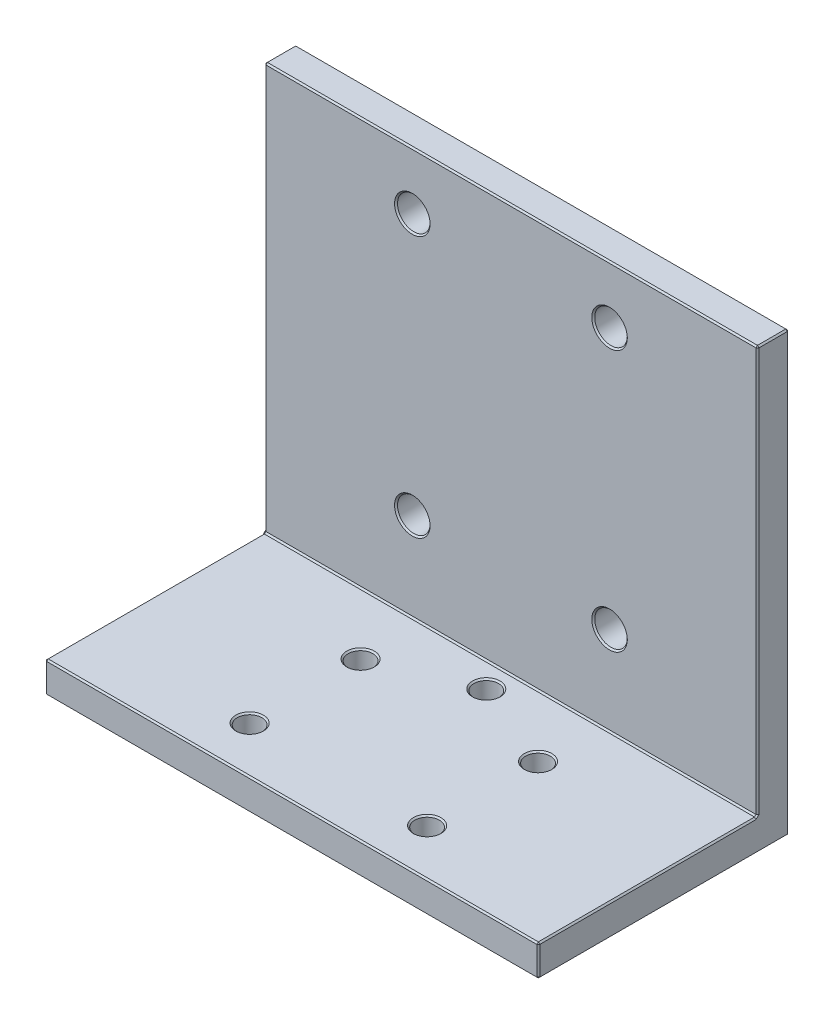
SolidWorks part; units mm, degrees
material "1060 Alloy"
ref_plane "Front Plane" through (0, 0, 0) normal (0, 0, 1) x (1, 0, 0)
ref_plane "Top Plane" through (0, 0, 0) normal (0, 1, 0) x (1, 0, 0)
ref_plane "Right Plane" through (0, 0, 0) normal (1, 0, 0) x (0, 0, -1)
sketch "Sketch1" plane through (0, 0, 0) normal (1, 0, 0) x (0, 0, -1)
  line L2 (0, 0) -> (0, 88.9)
  line L3 (0, 88.9) -> (-6.35, 88.9)
  line L4 (-6.35, 6.35) -> (-6.35, 88.9)
  line L5 (0, 0) -> (-50.8, 0)
  line L7 (-6.35, 6.35) -> (-50.8, 6.35)
  line L8 (-50.8, 0) -> (-50.8, 6.35)
  dimension "D1" = 6.35
  dimension "D2" = 88.9
  dimension "D3" = 50.8
extrude "Boss-Extrude1" add sketch "Sketch1" along normal mid plane 100
sketch "Sketch2" plane through (0, 0, 6.35) normal (0, 0, 1) x (1, 0, 0)
  line L0 (50, 0) -> (-50, 0) construction
  line L1 (20, 24.3) -> (-20, 24.3) construction
  line L2 (20, 24.3) -> (20, 77.3) construction
  line L3 (20, 77.3) -> (-20, 77.3) construction
  line L4 (-20, 24.3) -> (-20, 77.3) construction
  line L5 (20, 24.3) -> (-20, 77.3) construction
  line L6 (20, 77.3) -> (-20, 24.3) construction
  line L7 (50, 88.9) -> (50, 6.35) construction
  line L8 (0, 50.8) -> (0, 0) construction
  line L9 (-50, 101.6) -> (50, 101.6) construction
  line L10 (-50, 101.6) -> (-50, 0) construction
  line L11 (-50, 0) -> (50, 0) construction
  line L12 (50, 101.6) -> (50, 0) construction
  line L13 (-50, 88.9) -> (-50, 6.35) construction
  circle A0 centre (-20, 77.3) radius 3.3
  circle A1 centre (20, 77.3) radius 3.3
  circle A2 centre (20, 24.3) radius 3.3
  circle A3 centre (-20, 24.3) radius 3.3
  point P0 (0, 50.8)
  dimension "D1" = 6.6
  dimension "D2" = 40
  dimension "D3" = 53
  dimension "D5" = 101.6
  dimension "D4" = 50.8
extrude "Cut-Extrude1" cut sketch "Sketch2" against normal blind 100
sketch "Sketch3" plane through (0, 6.35, 0) normal (0, 1, 0) x (1, 0, 0)
  line L0 (0, 0) -> (0, -30.1) construction
  line L1 (18, -18.85) -> (-18, -18.85) construction
  line L2 (18, -18.85) -> (18, -41.35) construction
  line L3 (18, -41.35) -> (-18, -41.35) construction
  line L4 (-18, -18.85) -> (-18, -41.35) construction
  line L5 (18, -18.85) -> (-18, -41.35) construction
  line L6 (18, -41.35) -> (-18, -18.85) construction
  line L9 (50, 0) -> (-50, 0) construction
  circle A0 centre (-18, -18.85) radius 2.5
  circle A1 centre (-18, -41.35) radius 2.5
  circle A2 centre (18, -41.35) radius 2.5
  circle A3 centre (18, -18.85) radius 2.5
  circle A4 centre (0, -11.35) radius 2.5
  point P0 (0, -30.1)
  dimension "D1" = 5
  dimension "D2" = 22.5
  dimension "D3" = 36
  dimension "D4" = 7.5
  dimension "D5" = 11.35
extrude "Cut-Extrude2" cut sketch "Sketch3" against normal blind 100
chamfer "Chamfer1" distance 0.3 angle 45 36 edges at (-18, 6.35, 21.35) (-18, 6.35, 43.85) (18, 6.35, 43.85) (18, 6.35, 21.35) (0, 6.35, 13.85) (-16.7, 77.3, 6.35) (23.3, 77.3, 6.35) (23.3, 24.3, 6.35) (-16.7, 24.3, 6.35) (50, 6.35, 28.575) (0, 6.35, 50.8) (-50, 6.35, 28.575) (0, 88.9, 6.35) (50, 47.625, 6.35) (0, 6.35, 6.35) (-50, 47.625, 6.35) (0, 0, 0) (0, 88.9, 0) (50, 3.175, 50.8) (50, 88.9, 3.175) (50, 44.45, 0) (50, 0, 25.4) (0, 0, 50.8) (-50, 3.175, 50.8) (-50, 88.9, 3.175) (-50, 44.45, 0) (-50, 0, 25.4) (-16.7, 77.3, 0) (23.3, 77.3, 0) (23.3, 24.3, 0) (-16.7, 24.3, 0) (-18, 0, 21.35) (-18, 0, 43.85) (18, 0, 43.85) (18, 0, 21.35) (0, 0, 13.85)
equation "\"M5_tap\"=4.2mm       ' Below you can do mesurements as follows: cm, mm, ft, in, m, "
equation "\"M5_clearence\"=5.5mm"
equation "\"M6_tap\"=5mm"
equation "\"M6_clearence\"=6.6mm"
equation "\"D1@Sketch2\"=\"M6_clearence\""
equation "\"D1@Sketch3\"=\"M6_tap\""
equation "\"work_area_width\"=1100mm"
equation "\"work_area_depth\"=900mm"
equation "\"steel_base_width\"=3in "
equation "\"steel_base_height\"=2in"
equation "\"steel_base_wall_thickness\"=0.125in"
equation "\"steel_base_radius\"=6mm"
equation "\"steel_sides_width\"=3in     'this tube is rotated so flip width/height"
equation "\"steel_sides_height\"=2in    'this tube is rotated so flip width/height"
equation "\"steel_sides_wall_thickness\"=0.125in"
equation "\"steel_sides_radius\"=6mm"
equation "\"steel_gantry_width\"=4in    'this tube is rotated so flip width/height"
equation "\"steel_gantry_height\"=3in    'this tube is rotated so flip width/height"
equation "\"steel_gantry_wall_thickness\"=0.125in"
equation "\"steel_gantry_radius\"=6mm"
equation "\"steel_rollers_width\"=3in"
equation "\"steel_rollers_height\"=2in    'keep as low as possible as this increases how big plastic parts are"
equation "\"steel_rollers_wall_thickness\"=0.125in"
equation "\"steel_rollers_radius\"=6mm"
equation "\"steel_zbox_width\"=4in     'if the gantry height (rotated) is too thick, a wider zbox is necessary"
equation "\"steel_zbox_height\"=2in     'hole patteren changes as the zbox and gantry height (rotated) changes."
equation "\"steel_zbox_wall_thickness\"=0.125in"
equation "\"steel_zbox_radius\"=6mm"
equation "\"alu_zangle_width\"=3.5in     'check that it doesn't interfer with the gantry"
equation "\"alu_zangle_height\"=2in"
equation "\"alu_zangle_wall_thickness\"=0.25in   'check that it doesn't interfer with the gantry"
equation "\"D1@Sketch1\"=\"alu_zangle_wall_thickness\""
equation "\"D2@Sketch1\"=\"alu_zangle_width\""
equation "\"D3@Sketch1\"=\"alu_zangle_height\""
equation "\"D5@Sketch2\"=\"steel_zbox_width\""
equation "\"D5@Sketch3\"=\"alu_zangle_wall_thickness\"+5"
equation "\"D4@Sketch2\"=\"steel_zbox_width\"/2"
